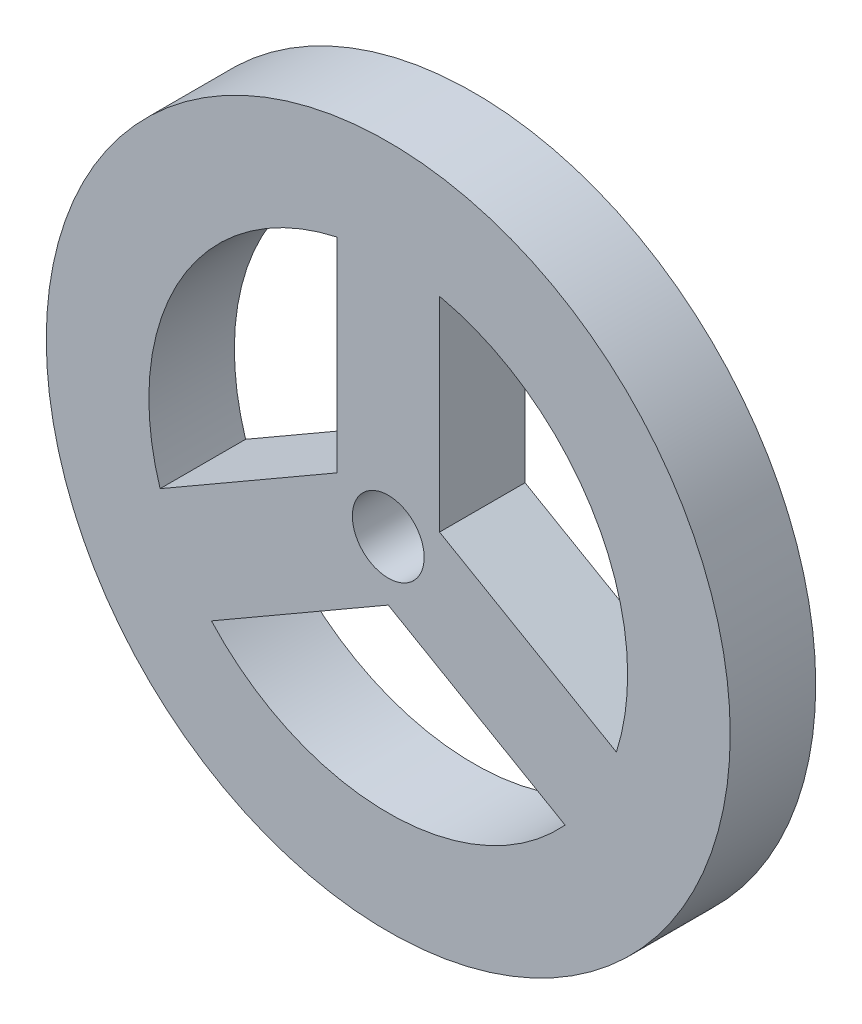
SolidWorks part; units mm, degrees
ref_plane "Front Plane" through (0, 0, 0) normal (0, 0, 1) x (1, 0, 0)
ref_plane "Top Plane" through (0, 0, 0) normal (0, 1, 0) x (1, 0, 0)
ref_plane "Right Plane" through (0, 0, 0) normal (1, 0, 0) x (0, 0, -1)
sketch "Sketch1" plane through (0, 0, 0) normal (0, 0, 1) x (1, 0, 0)
  line L0 (0, 0) -> (0, 17.78) construction
  line L1 (0, 0) -> (15.3979, -8.89) construction
  line L2 (0, 0) -> (-15.3979, -8.89) construction
  line L3 (-3.81, 2.1997) -> (-17.3029, -5.5904)
  line L4 (0, -4.3994) -> (13.4929, -12.1896)
  line L5 (3.81, 2.1997) -> (3.81, 17.78)
  line L6 (0, -4.3994) -> (-13.4929, -12.1896)
  line L7 (3.81, 2.1997) -> (17.3029, -5.5904)
  line L8 (-3.81, 2.1997) -> (-3.81, 17.78)
  line L9 (1.905, 3.2996) -> (17.3029, -5.5904) construction
  line L10 (3.81, 0) -> (3.81, 17.78) construction
  line L11 (-1.905, 3.2996) -> (-17.3029, -5.5904) construction
  line L12 (-3.81, 0) -> (-3.81, 17.78) construction
  line L13 (-1.905, -3.2996) -> (13.4929, -12.1896) construction
  line L14 (1.905, -3.2996) -> (-13.4929, -12.1896) construction
  circle A0 centre (0, 0) radius 25.4
  circle A1 centre (0, 0) radius 2.667
  arc A3 (-13.1353, -11.9831) -> (13.1353, -11.9831) centre (0, 0) ccw
  arc A4 (16.9453, -5.3839) -> (3.81, 17.367) centre (0, 0) ccw
  arc A5 (-3.81, 17.367) -> (-16.9453, -5.3839) centre (0, 0) ccw
  point P12 (0, 0)
  dimension "D1" = 50.8
  dimension "D2" = 5.334
  dimension "D3" = 7.62
  dimension "D5" = 3.81
  dimension "D6" = 3.81
  dimension "D4" = 3
extrude "Boss-Extrude3" add sketch "Sketch1" along normal blind 6.35 contours A0 A5 L8 L3 A4 L7 L5 A3 L6 L4 A1 region at (-24.6816, 0, 0)
equation "\"rodThick\"= 0.085in"
equation "\"clear\"= 0.003in"
